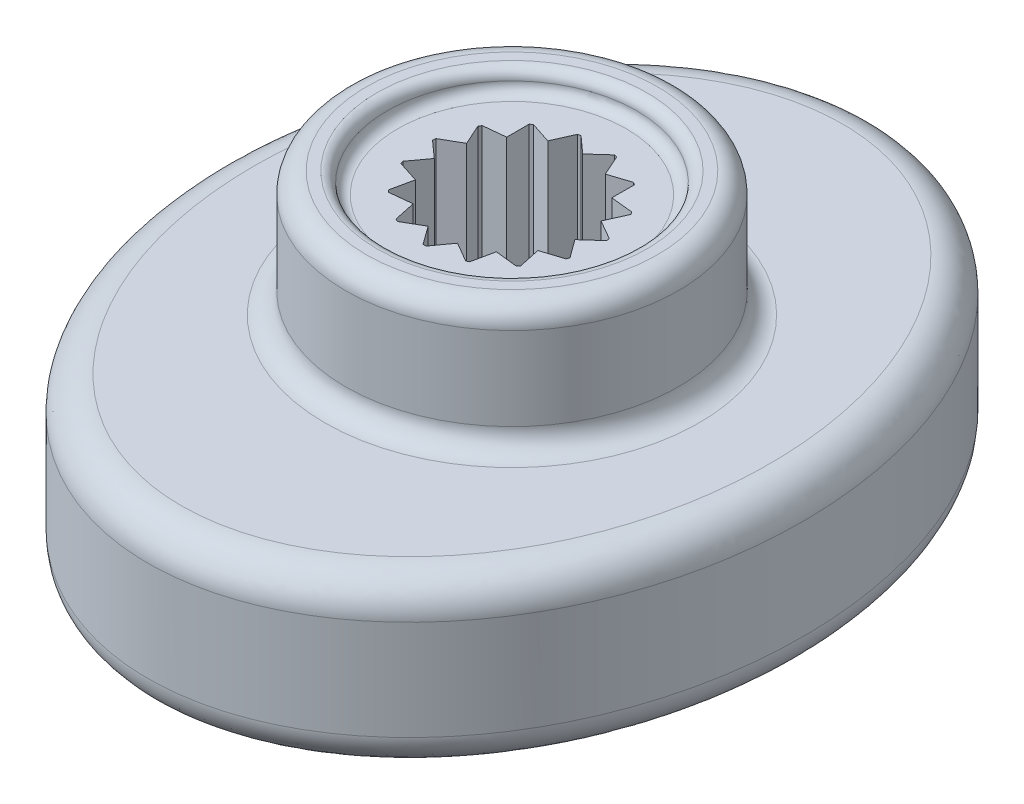
SolidWorks part; units mm, degrees
ref_plane "Front Plane" through (0, 0, 0) normal (0, 0, 1) x (1, 0, 0)
ref_plane "Top Plane" through (0, 0, 0) normal (0, 1, 0) x (1, 0, 0)
ref_plane "Right Plane" through (0, 0, 0) normal (1, 0, 0) x (0, 0, -1)
sketch "Sketch1" plane through (0, 0, 0) normal (0, 1, 0) x (1, 0, 0)
  line L0 (-7, 0) -> (7, 0) construction
  circle A7 centre (0, 0) radius 0.75
  ellipse E0 centre (0, 0) end of major axis (0, 8.75) minor radius 7
  dimension "D1" = 1.5
  dimension "D3" = 17.5
  dimension "12" = 14
extrude "Boss-Extrude1" add sketch "Sketch1" along normal blind 2 and the other way blind 2
fillet "Fillet1" radius 0.8 2 edges at (0, -2, -8.75) (0, 2, -8.75)
sketch "Sketch2" plane through (0, 2, 0) normal (0, 1, 0) x (1, 0, 0)
  circle A0 centre (0, 0) radius 4
  circle A1 centre (0, 0) radius 2.1
  dimension "D1" = 8
  dimension "D2" = 4.2
extrude "Boss-Extrude2" add sketch "Sketch2" along normal offset from surface (3 mm away) 5 up to plane "Top Plane"
sketch "Sketch5" plane through (0, 2, 0) normal (0, 1, 0) x (1, 0, 0)
  circle A0 centre (0, 0) radius 2.1
  circle A1 centre (0, 0) radius 2.1 construction
extrude "Cut-Extrude2" cut sketch "Sketch5" against normal blind 1
sketch "Sketch4" plane through (0, 1, 0) normal (0, 1, 0) x (1, 0, 0)
  line L0 (0, 0) -> (0, 2.1) construction
  line L1 (-0.4, 2.0616) -> (0, 1.7)
  line L2 (0, 1.7) -> (0.4, 2.0616)
  line L3 (0.6915, 1.553) -> (1.2039, 1.7206)
  line L4 (0.4731, 2.046) -> (0.6915, 1.553)
  line L5 (1.2633, 1.1375) -> (1.7997, 1.0822)
  line L6 (1.2644, 1.6767) -> (1.2633, 1.1375)
  line L7 (1.6168, 0.5253) -> (2.0843, 0.2566)
  line L8 (1.837, 1.0175) -> (1.6168, 0.5253)
  line L9 (1.6907, -0.1777) -> (2.0084, -0.6133)
  line L10 (2.0921, 0.1823) -> (1.6907, -0.1777)
  line L11 (1.4722, -0.85) -> (1.5854, -1.3772)
  line L12 (1.9854, -0.6844) -> (1.4722, -0.85)
  line L13 (0.9992, -1.3753) -> (0.8881, -1.9029)
  line L14 (1.5354, -1.4327) -> (0.9992, -1.3753)
  line L15 (0.3534, -1.6629) -> (0.0374, -2.0997)
  line L16 (0.8199, -1.9333) -> (0.3534, -1.6629)
  line L17 (-0.3534, -1.6629) -> (-0.8199, -1.9333)
  line L18 (-0.0374, -2.0997) -> (-0.3534, -1.6629)
  line L19 (-0.9992, -1.3753) -> (-1.5354, -1.4327)
  line L20 (-0.8881, -1.9029) -> (-0.9992, -1.3753)
  line L21 (-1.4722, -0.85) -> (-1.9854, -0.6844)
  line L22 (-1.5854, -1.3772) -> (-1.4722, -0.85)
  line L23 (-1.6907, -0.1777) -> (-2.0921, 0.1823)
  line L24 (-2.0084, -0.6133) -> (-1.6907, -0.1777)
  line L25 (-1.6168, 0.5253) -> (-1.837, 1.0175)
  line L26 (-2.0843, 0.2566) -> (-1.6168, 0.5253)
  line L27 (-1.2633, 1.1375) -> (-1.2644, 1.6767)
  line L28 (-1.7997, 1.0822) -> (-1.2633, 1.1375)
  line L29 (-0.6915, 1.553) -> (-0.4731, 2.046)
  line L30 (-1.2039, 1.7206) -> (-0.6915, 1.553)
  circle A0 centre (0, 0) radius 2.1 construction
  arc A1 (-0.4, 2.0616) -> (0.4, 2.0616) centre (0, 0) cw
  arc A2 (0.4731, 2.046) -> (1.2039, 1.7206) centre (0, 0) cw
  arc A3 (1.2644, 1.6767) -> (1.7997, 1.0822) centre (0, 0) cw
  arc A4 (1.837, 1.0175) -> (2.0843, 0.2566) centre (0, 0) cw
  arc A5 (2.0921, 0.1823) -> (2.0084, -0.6133) centre (0, 0) cw
  arc A6 (1.9854, -0.6844) -> (1.5854, -1.3772) centre (0, 0) cw
  arc A7 (1.5354, -1.4327) -> (0.8881, -1.9029) centre (0, 0) cw
  arc A8 (0.8199, -1.9333) -> (0.0374, -2.0997) centre (0, 0) cw
  arc A9 (-0.0374, -2.0997) -> (-0.8199, -1.9333) centre (0, 0) cw
  arc A10 (-0.8881, -1.9029) -> (-1.5354, -1.4327) centre (0, 0) cw
  arc A11 (-1.5854, -1.3772) -> (-1.9854, -0.6844) centre (0, 0) cw
  arc A12 (-2.0084, -0.6133) -> (-2.0921, 0.1823) centre (0, 0) cw
  arc A13 (-2.0843, 0.2566) -> (-1.837, 1.0175) centre (0, 0) cw
  arc A14 (-1.7997, 1.0822) -> (-1.2644, 1.6767) centre (0, 0) cw
  arc A15 (-1.2039, 1.7206) -> (-0.4731, 2.046) centre (0, 0) cw
  circle A16 centre (0, 0) radius 2.1 construction
  point P8 (0, 2.1)
  point P54 (0, 0)
  dimension "D1" = 1.7
  dimension "D2" = 0.8
  dimension "D4" = 15
extrude "Boss-Extrude3" add sketch "Sketch4" along normal blind 3.5
fillet "Fillet2" radius 0.5 2 edges at (0, 5, 4) (0, 2, 4)
sketch "Sketch6" plane through (0, 5, 0) normal (0, 1, 0) x (1, 0, 0)
  circle A0 centre (0, 0) radius 2.1
  circle A1 centre (0, 0) radius 3
  circle A2 centre (0, 0) radius 2.1 construction
  dimension "D1" = 6
extrude "Cut-Extrude3" cut sketch "Sketch6" against normal blind 0.5
fillet "Fillet3" radius 0.25 2 edges at (0, 5, 3) (0, 4.5, 3)
